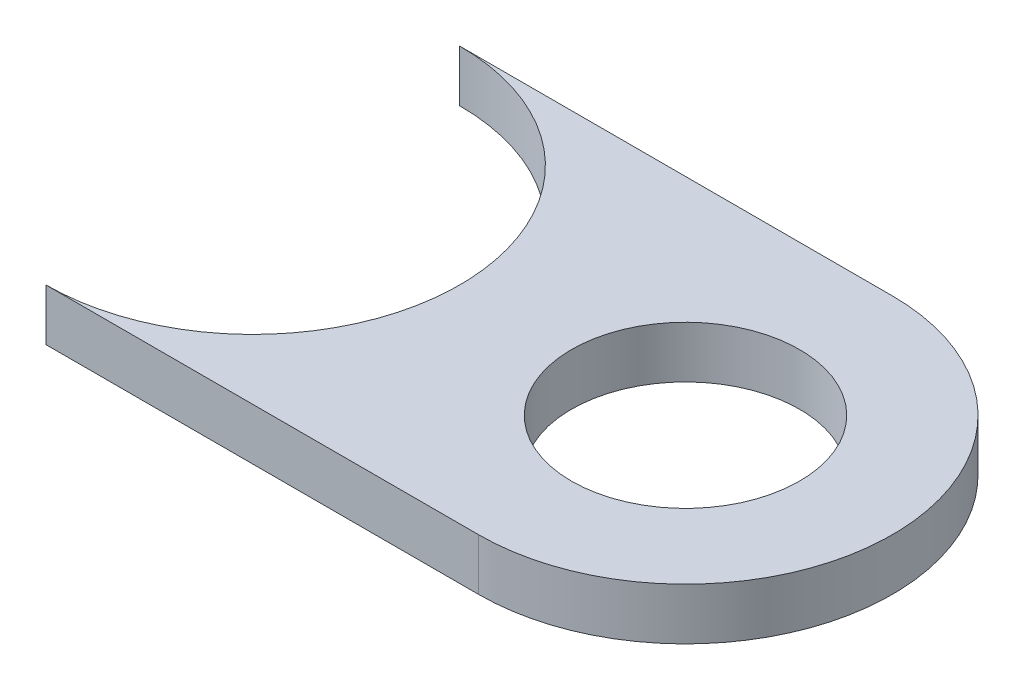
SolidWorks part; units mm, degrees
ref_plane "Front Plane" through (0, 0, 0) normal (0, 0, 1) x (1, 0, 0)
ref_plane "Top Plane" through (0, 0, 0) normal (0, 1, 0) x (1, 0, 0)
ref_plane "Right Plane" through (0, 0, 0) normal (1, 0, 0) x (0, 0, -1)
sketch "Sketch1" plane through (0, 0, 0) normal (0, 1, 0) x (1, 0, 0)
  line L0 (0, 0) -> (-26.5608, 0) construction
  line L1 (-26.5608, 12.7) -> (0, 12.7)
  line L2 (-26.5608, -12.7) -> (0, -12.7)
  circle A0 centre (0, 0) radius 7.0002
  arc A1 (-26.5608, -12.7) -> (-26.5608, 12.7) centre (-26.5608, 0) ccw
  arc A2 (0, -12.7) -> (0, 12.7) centre (0, 0) ccw
extrude "Boss-Extrude1" add sketch "Sketch1" along normal blind 3.175
sketch "Sketch2" plane through (0, 3.175, 0) normal (0, 1, 0) x (1, 0, 0)
  line L0 (0, -12.7) -> (0, -9.525)
  line L1 (0, -9.525) -> (-18.1605, -9.525)
  arc A0 (-26.5608, -12.7) -> (-26.5608, 12.7) centre (-26.5608, 0) ccw construction
  point P8 (0, 0)
  dimension "D1" = 18.1605
